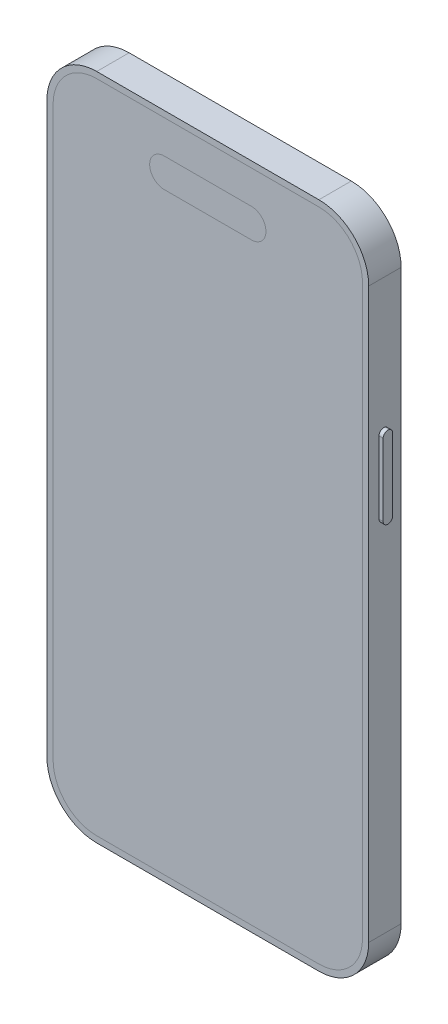
SolidWorks part; units mm, degrees
ref_plane "前视基准面" through (0, 0, 0) normal (0, 0, 1) x (1, 0, 0)
ref_plane "上视基准面" through (0, 0, 0) normal (0, 1, 0) x (1, 0, 0)
ref_plane "右视基准面" through (0, 0, 0) normal (1, 0, 0) x (0, 0, -1)
other "Configuration Table"
sketch "草图1" plane through (0, 0, 0) normal (0, 0, 1) x (1, 0, 0)
  line L1 (26.75, -80.45) -> (-26.75, -80.45)
  line L2 (38.75, -68.45) -> (38.75, 68.45)
  line L3 (26.75, 80.45) -> (-26.75, 80.45)
  line L4 (-38.75, -68.45) -> (-38.75, 68.45)
  line L5 (38.75, -80.45) -> (-38.75, 80.45) construction
  line L6 (38.75, 80.45) -> (-38.75, -80.45) construction
  arc A0 (-26.75, -80.45) -> (-38.75, -68.45) centre (-26.75, -68.45) cw
  arc A1 (38.75, 68.45) -> (26.75, 80.45) centre (26.75, 68.45) ccw
  arc A2 (-26.75, 80.45) -> (-38.75, 68.45) centre (-26.75, 68.45) ccw
  arc A3 (26.75, -80.45) -> (38.75, -68.45) centre (26.75, -68.45) ccw
  point P0 (0, 0)
  dimension "D1" = 12
  dimension "D2" = 12
  dimension "D3" = 12
extrude "凸台-拉伸1" add sketch "草图1" along normal blind 7.8
sketch "草图3" plane through (0, 0, 7.8) normal (0, 0, 1) x (1, 0, 0)
  line L0 (-10.5, 67.45) -> (10.5, 67.45) construction
  line L1 (-10.5, 70.95) -> (10.5, 70.95)
  line L2 (-10.5, 63.95) -> (10.5, 63.95)
  line L3 (26.75, 80.45) -> (-26.75, 80.45) construction
  arc A0 (-10.5, 70.95) -> (-10.5, 63.95) centre (-10.5, 67.45) ccw
  arc A1 (10.5, 63.95) -> (10.5, 70.95) centre (10.5, 67.45) ccw
  point P2 (0, 67.45)
  point P9 (0, 67.45)
  dimension "D1" = 3.5
  dimension "D2" = 21
  dimension "D3" = 9.5
split line "分割线2"
sketch "草图8" plane through (0, 0, 7.8) normal (0, 0, 1) x (1, 0, 0)
  line L0 (38.75, -68.45) -> (38.75, 68.45) construction
  line L1 (-26.75, -80.45) -> (26.75, -80.45) construction
  line L2 (-38.75, 68.45) -> (-38.75, -68.45) construction
  line L3 (26.75, 80.45) -> (-26.75, 80.45) construction
  line L4 (38.75, -68.45) -> (38.75, 68.45)
  line L5 (-26.75, -80.45) -> (26.75, -80.45)
  line L6 (-38.75, 68.45) -> (-38.75, -68.45)
  line L7 (26.75, 80.45) -> (-26.75, 80.45)
  line L8 (37.25, -68.45) -> (37.25, 68.45)
  line L9 (26.75, 78.95) -> (-26.75, 78.95)
  line L10 (-37.25, 68.45) -> (-37.25, -68.45)
  line L11 (-26.75, -78.95) -> (26.75, -78.95)
  arc A0 (38.75, 68.45) -> (26.75, 80.45) centre (26.75, 68.45) ccw construction
  arc A1 (26.75, -80.45) -> (38.75, -68.45) centre (26.75, -68.45) ccw construction
  arc A2 (-38.75, -68.45) -> (-26.75, -80.45) centre (-26.75, -68.45) ccw construction
  arc A3 (-26.75, 80.45) -> (-38.75, 68.45) centre (-26.75, 68.45) ccw construction
  arc A4 (38.75, 68.45) -> (26.75, 80.45) centre (26.75, 68.45) ccw
  arc A5 (26.75, -80.45) -> (38.75, -68.45) centre (26.75, -68.45) ccw
  arc A6 (-38.75, -68.45) -> (-26.75, -80.45) centre (-26.75, -68.45) ccw
  arc A7 (-26.75, 80.45) -> (-38.75, 68.45) centre (-26.75, 68.45) ccw
  arc A8 (37.25, 68.45) -> (26.75, 78.95) centre (26.75, 68.45) ccw
  arc A9 (-26.75, 78.95) -> (-37.25, 68.45) centre (-26.75, 68.45) ccw
  arc A10 (-37.25, -68.45) -> (-26.75, -78.95) centre (-26.75, -68.45) ccw
  arc A11 (26.75, -78.95) -> (37.25, -68.45) centre (26.75, -68.45) ccw
  dimension "D1" = 1.5
split line "分割线5"
sketch "草图9" plane through (0, 0, 0) normal (0, 0, -1) x (-1, 0, 0)
  line L0 (-38.75, -68.45) -> (-38.75, 68.45) construction
  line L1 (-26.75, 80.45) -> (26.75, 80.45) construction
  line L2 (-27.75, 75.45) -> (-5.75, 75.45)
  line L3 (-35.75, 67.45) -> (-35.75, 45.45)
  line L4 (-27.75, 37.45) -> (-5.75, 37.45)
  line L5 (2.25, 67.45) -> (2.25, 45.45)
  line L6 (-35.75, 75.45) -> (2.25, 37.45) construction
  line L7 (-35.75, 37.45) -> (2.25, 75.45) construction
  line L8 (-25.75, 65.45) -> (-25.75, 47.45) construction
  line L9 (-25.75, 47.45) -> (-7.75, 57.3607) construction
  line L10 (-7.75, 57.3607) -> (-25.75, 65.45) construction
  circle A0 centre (-25.75, 65.45) radius 8.1914
  circle A1 centre (-7.75, 57.3607) radius 8.1914
  circle A2 centre (-25.75, 47.45) radius 8.1914
  arc A3 (-5.75, 75.45) -> (2.25, 67.45) centre (-5.75, 67.45) cw
  arc A4 (2.25, 45.45) -> (-5.75, 37.45) centre (-5.75, 45.45) cw
  arc A5 (-27.75, 37.45) -> (-35.75, 45.45) centre (-27.75, 45.45) cw
  arc A6 (-35.75, 67.45) -> (-27.75, 75.45) centre (-27.75, 67.45) cw
  circle A7 centre (-9.3604, 69.3607) radius 1.75
  point P1 (-16.75, 56.45)
  dimension "D7" = 8
  dimension "D1" = 38
  dimension "D2" = 38
  dimension "D3" = 3
  dimension "D4" = 5
  dimension "D5" = 18
  dimension "D6" = 18
  dimension "D8" = 12
extrude "凸台-拉伸3" add sketch "草图9" along normal blind 1.2 contours L2 A3 L5 A4 L4 A5 L3 A6
extrude "凸台-拉伸4" add sketch "草图9<4>" along normal blind 4 contours A0 | A2 | A1
sketch "草图9<4>" plane through (0, 0, 0) normal (0, 0, -1) x (-1, 0, 0) same geometry as "草图9"
extrude "凸台-拉伸5" add sketch "草图9<5>" along normal blind 3 contours A7
sketch "草图9<5>" plane through (0, 0, 0) normal (0, 0, -1) x (-1, 0, 0) same geometry as "草图9"
sketch "草图10" plane through (0, 0, -4) normal (0, 0, -1) x (-1, 0, 0)
  circle A0 centre (-25.75, 65.45) radius 7.1914
  circle A1 centre (-25.75, 65.45) radius 8.1914
  circle A2 centre (-25.75, 65.45) radius 8.1914
  circle A3 centre (-25.75, 47.45) radius 8.1914
  circle A4 centre (-25.75, 47.45) radius 8.1914
  circle A5 centre (-7.75, 57.3607) radius 8.1914
  circle A6 centre (-7.75, 57.3607) radius 8.1914
  circle A7 centre (-7.75, 57.3607) radius 7.1914
  circle A8 centre (-25.75, 47.45) radius 7.1914
  dimension "D1" = 0
  dimension "D2" = 0
  dimension "D3" = 0
  dimension "D4" = 1
split line "分割线6"
sketch "草图11" plane through (0, 0, -1.2) normal (0, 0, -1) x (-1, 0, 0)
  circle A0 centre (-9.6875, 42.9368) radius 1.062
sketch "草图12" plane through (-38.75, 0, 0) normal (-1, 0, 0) x (0, 0, 1)
  line L0 (3.5502, 51.6999) -> (3.5502, 46.1585) construction
  line L1 (4.6865, 51.6999) -> (4.6865, 46.1585)
  line L2 (2.414, 51.6999) -> (2.414, 46.1585)
  line L3 (3.5502, 27.927) -> (3.5502, 39.0276) construction
  line L4 (2.5852, 27.927) -> (2.5852, 39.0276)
  line L5 (4.5153, 27.927) -> (4.5153, 39.0276)
  line L6 (3.5502, 8.7601) -> (3.5502, 22.3885) construction
  line L7 (2.3459, 8.7601) -> (2.3459, 22.3885)
  line L8 (4.7546, 8.7601) -> (4.7546, 22.3885)
  arc A0 (4.6865, 51.6999) -> (2.414, 51.6999) centre (3.5502, 51.6999) ccw
  arc A1 (2.414, 46.1585) -> (4.6865, 46.1585) centre (3.5502, 46.1585) ccw
  arc A2 (2.5852, 27.927) -> (4.5153, 27.927) centre (3.5502, 27.927) ccw
  arc A3 (4.5153, 39.0276) -> (2.5852, 39.0276) centre (3.5502, 39.0276) ccw
  arc A4 (2.3459, 8.7601) -> (4.7546, 8.7601) centre (3.5502, 8.7601) ccw
  arc A5 (4.7546, 22.3885) -> (2.3459, 22.3885) centre (3.5502, 22.3885) ccw
  point P2 (3.5502, 48.9292)
  point P7 (3.5502, 33.4773)
  point P14 (3.5502, 15.5743)
  point P21 (0, 0)
extrude "凸台-拉伸7" add sketch "草图12" along normal blind 1 contours L1 A1 L2 A0
extrude "凸台-拉伸8" add sketch "草图12<3>" along normal blind 1
sketch "草图12<3>" plane through (-38.75, 0, 0) normal (-1, 0, 0) x (0, 0, 1) same geometry as "草图12"
sketch "草图13" plane through (38.75, 0, 0) normal (1, 0, 0) x (0, 0, -1)
  line L0 (-4.183, 35.9577) -> (-4.183, 18.6067) construction
  line L1 (-3.0415, 35.9577) -> (-3.0415, 18.6067)
  line L2 (-5.3245, 35.9577) -> (-5.3245, 18.6067)
  arc A0 (-3.0415, 35.9577) -> (-5.3245, 35.9577) centre (-4.183, 35.9577) ccw
  arc A1 (-5.3245, 18.6067) -> (-3.0415, 18.6067) centre (-4.183, 18.6067) ccw
  point P2 (-4.183, 27.2822)
  point P7 (0, 0)
extrude "凸台-拉伸9" add sketch "草图13" along normal blind 1
extrude "凸台-拉伸10" add sketch "草图11" along normal blind 0.08 contours A0
equation "\"1.2.00mm\"=1"
